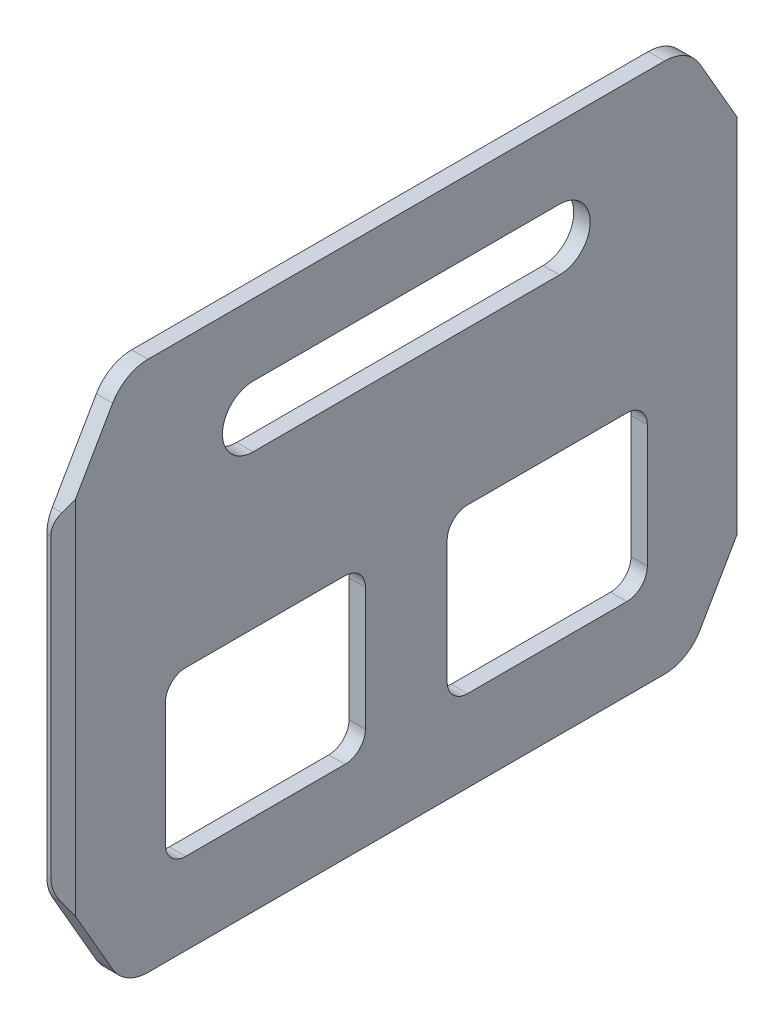
SolidWorks part; units mm, degrees
ref_plane "Front Plane" through (0, 0, 0) normal (0, 0, 1) x (1, 0, 0)
ref_plane "Top Plane" through (0, 0, 0) normal (0, 1, 0) x (1, 0, 0)
ref_plane "Right Plane" through (0, 0, 0) normal (1, 0, 0) x (0, 0, -1)
sketch "Sketch1" plane through (0, 0, 0) normal (1, 0, 0) x (0, 0, -1)
  line L0 (0, 254) -> (0, 0) construction
  line L2 (-213.36, 0) -> (-213.36, 254)
  line L4 (213.36, 0) -> (213.36, 254)
  line L5 (-95.25, 215.9) -> (95.25, 215.9) construction
  line L6 (-95.25, 234.95) -> (95.25, 234.95)
  line L7 (-95.25, 196.85) -> (95.25, 196.85)
  line L8 (-213.36, 127) -> (213.36, 127) construction
  line L13 (213.36, 0) -> (-213.36, 0) construction
  line L15 (213.36, 0) -> (213.36, -50.8)
  line L16 (213.36, -50.8) -> (-213.36, -50.8)
  line L18 (-213.36, 0) -> (-213.36, -50.8)
  line L19 (-213.36, 254) -> (213.36, 254) construction
  line L24 (38.1, 101.6) -> (137.16, 101.6)
  line L25 (-38.1, 0) -> (-137.16, 0)
  line L26 (-25.4, 12.7) -> (-25.4, 88.9)
  line L27 (-38.1, 101.6) -> (-137.16, 101.6)
  line L28 (-149.86, 12.7) -> (-149.86, 88.9)
  line L33 (149.86, 12.7) -> (149.86, 88.9)
  line L34 (38.1, 0) -> (137.16, 0)
  line L35 (25.4, 12.7) -> (25.4, 88.9)
  line L36 (-213.36, 254) -> (-213.36, 279.4)
  line L37 (-213.36, 279.4) -> (213.36, 279.4)
  line L38 (213.36, 254) -> (213.36, 279.4)
  line L46 (-213.36, 12.7) -> (213.36, 12.7) construction
  arc A0 (-95.25, 234.95) -> (-95.25, 196.85) centre (-95.25, 215.9) ccw
  arc A1 (95.25, 196.85) -> (95.25, 234.95) centre (95.25, 215.9) ccw
  arc A4 (149.86, 12.7) -> (137.16, 0) centre (137.16, 12.7) cw
  arc A5 (137.16, 101.6) -> (149.86, 88.9) centre (137.16, 88.9) cw
  arc A6 (38.1, 101.6) -> (25.4, 88.9) centre (38.1, 88.9) ccw
  arc A7 (38.1, 0) -> (25.4, 12.7) centre (38.1, 12.7) cw
  arc A8 (-38.1, 0) -> (-25.4, 12.7) centre (-38.1, 12.7) ccw
  arc A9 (-137.16, 0) -> (-149.86, 12.7) centre (-137.16, 12.7) cw
  arc A10 (-137.16, 101.6) -> (-149.86, 88.9) centre (-137.16, 88.9) ccw
  arc A11 (-25.4, 88.9) -> (-38.1, 101.6) centre (-38.1, 88.9) ccw
  point P10 (0, 215.9)
  point P58 (149.86, 0)
  point P61 (149.86, 101.6)
  point P64 (25.4, 101.6)
  point P67 (25.4, 0)
  point P70 (-25.4, 0)
  point P73 (-149.86, 0)
  point P76 (-149.86, 101.6)
  point P79 (-25.4, 101.6)
  dimension "D18" = 12.7
  dimension "D1" = 254
  dimension "D2" = 426.72
  dimension "D3" = 190.5
  dimension "D4" = 19.05
  dimension "D5" = 38.1
  dimension "D6" = 50.8
  dimension "D7" = 25.4
  dimension "D9" = 124.46
  dimension "D10" = 25.4
  dimension "D12" = 63.5
  dimension "D15" = 25.4
  dimension "D8" = 101.6
extrude "Boss-Extrude1" add sketch "Sketch1" along normal blind 10.16
sketch "Sketch2" plane through (0, 0, 0) normal (1, 0, 0) x (0, 0, -1)
  line L14 (-213.36, 127) -> (213.36, 127) construction
  line L15 (-196.85, 132.08) -> (-120.65, 132.08)
  line L16 (-196.85, 132.08) -> (-196.85, 121.92)
  line L17 (-196.85, 121.92) -> (-120.65, 121.92)
  line L18 (-120.65, 132.08) -> (-120.65, 121.92)
  line L19 (-213.36, 0) -> (-213.36, 254) construction
  line L20 (-38.1, 132.08) -> (38.1, 132.08)
  line L21 (-38.1, 132.08) -> (-38.1, 121.92)
  line L22 (38.1, 132.08) -> (38.1, 121.92)
  line L23 (-38.1, 121.92) -> (38.1, 121.92)
  line L24 (120.65, 132.08) -> (196.85, 132.08)
  line L25 (120.65, 132.08) -> (120.65, 121.92)
  line L26 (196.85, 132.08) -> (196.85, 121.92)
  line L27 (120.65, 121.92) -> (196.85, 121.92)
  point P6 (-196.85, 127)
  dimension "D1" = 16.51
  dimension "D2" = 10.16
  dimension "D3" = 76.2
  dimension "D4" = 3
extrude "Cut-Extrude1" cut sketch "Sketch2" along normal blind 4.572
chamfer "Chamfer1" distance 38.1 angle 60 4 edges at (5.08, -50.8, 213.36) (5.08, -50.8, -213.36) (5.08, 279.4, 213.36) (5.08, 279.4, -213.36)
fillet "Fillet1" radius 25.4 8 edges at (5.08, 279.4, -175.26) (5.08, 213.4089, -213.36) (5.08, 15.1911, -213.36) (5.08, -50.8, -175.26) (5.08, -50.8, 175.26) (5.08, 15.1911, 213.36) (5.08, 213.4089, 213.36) (5.08, 279.4, 175.26)
chamfer "Chamfer2" distance 7.62 angle 45 2 edges at (10.16, 114.3, -213.36) (10.16, 114.3, 213.36)
sketch "Sketch3" plane through (0, 0, 0) normal (-1, 0, 0) x (0, 0, 1)
  line L0 (-114.3, 215.9) -> (-205.74, 215.9) construction
  arc A0 (-95.25, 234.95) -> (-95.25, 196.85) centre (-95.25, 215.9) ccw construction
  point P6 (167.5653, 121.0836)
